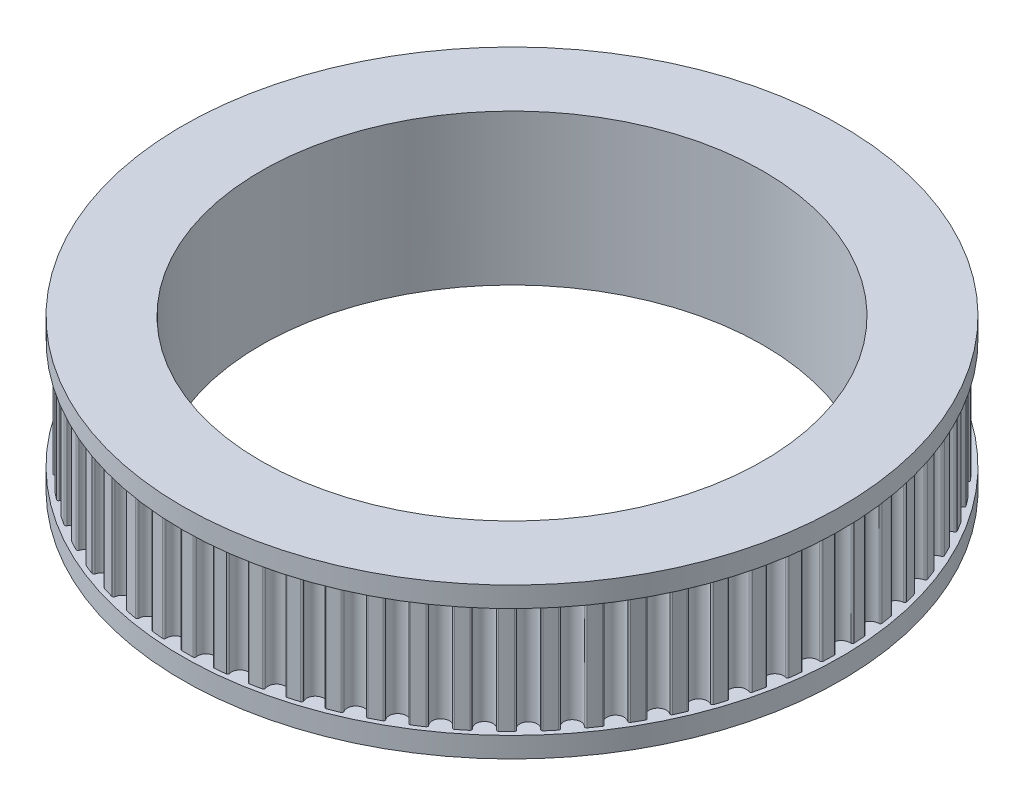
SolidWorks part; units mm, degrees
ref_plane "Front Plane" through (0, 0, 0) normal (0, 0, 1) x (1, 0, 0)
ref_plane "Top Plane" through (0, 0, 0) normal (0, 1, 0) x (1, 0, 0)
ref_plane "Right Plane" through (0, 0, 0) normal (1, 0, 0) x (0, 0, -1)
sketch "Sketch1" plane through (0, 0, 0) normal (0, 1, 0) x (1, 0, 0)
  circle A0 centre (0, 0) radius 16
  circle A1 centre (0, 0) radius 20.6901
  dimension "D1" = 32
  dimension "D2" = 41.3803
extrude "Boss-Extrude1" add sketch "Sketch1" along normal blind 7
sketch "Sketch2" plane through (0, 7, 0) normal (0, 1, 0) x (1, 0, 0)
  line L0 (0, 0) -> (0, 27.4541) construction
  arc A0 (-0.5185, 20.6836) -> (0.5185, 20.6836) centre (0, 20.5001) ccw
  circle A1 centre (0, 0) radius 20.6901
  arc A2 (0.5185, 20.6836) -> (-0.5185, 20.6836) centre (0, 0) ccw
  dimension "D2" = 1.1
  dimension "D3" = 20.5001
  dimension "D1" = 0
extrude "Cut-Extrude1" cut sketch "Sketch2" against normal through all
fillet "Fillet1" radius 0.1 2 edges at (0.5185, 3.5, -20.6836) (-0.5185, 3.5, -20.6836)
pattern_circular "CirPattern1" count 65 over 360 about axis through (0, 7, 0) along (0, 1, 0) of "Fillet1", "Cut-Extrude1"
sketch "Sketch3" plane through (0, 7, 0) normal (0, 1, 0) x (1, 0, 0)
  circle A0 centre (0, 0) radius 21
  circle A1 centre (0, 0) radius 16 construction
  circle A2 centre (0, 0) radius 16
  dimension "D1" = 42
extrude "Boss-Extrude2" add sketch "Sketch3" along normal blind 1.3
sketch "Sketch4" plane through (0, 0, 0) normal (0, -1, 0) x (1, 0, 0)
  circle A0 centre (0, 0) radius 16 construction
  circle A1 centre (0, 0) radius 16
  circle A2 centre (0, 0) radius 21
  dimension "D1" = 42
extrude "Boss-Extrude3" add sketch "Sketch4" along normal blind 1.3
